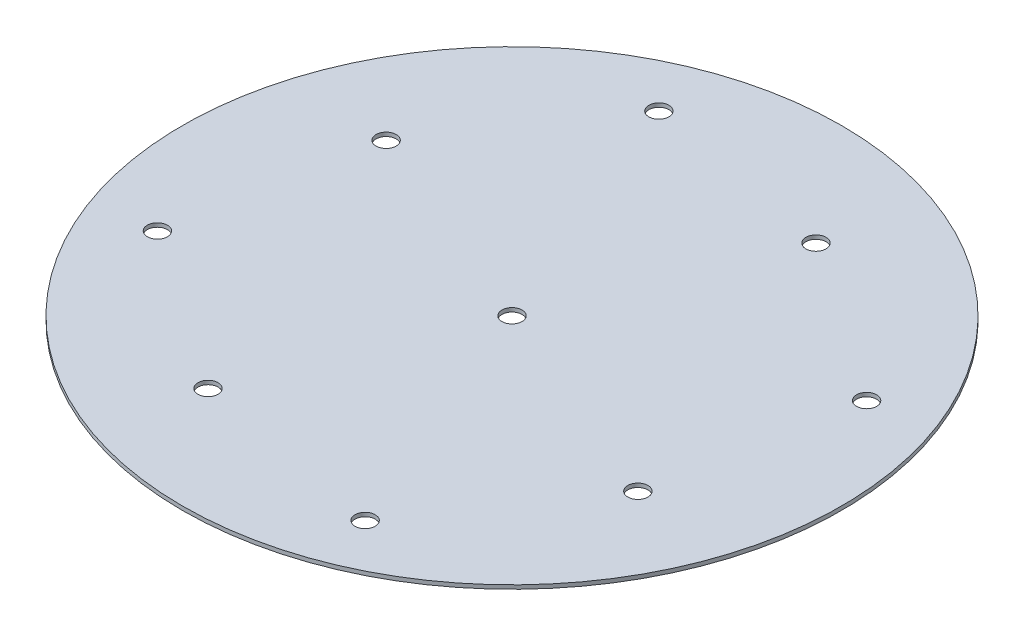
SolidWorks part; units mm, degrees
ref_plane "Front Plane" through (0, 0, 0) normal (0, 0, 1) x (1, 0, 0)
ref_plane "Top Plane" through (0, 0, 0) normal (0, 1, 0) x (1, 0, 0)
ref_plane "Right Plane" through (0, 0, 0) normal (1, 0, 0) x (0, 0, -1)
sketch "Sketch2" plane through (0, 0, 0) normal (1, 0, 0) x (0, 0, -1)
  line L0 (0, 0) -> (-84.9998, 0)
  line L1 (-84.9998, 0) -> (-84.9998, 1)
  line L2 (-84.9998, 1) -> (0, 1)
  line L5 (0, 1) -> (0, 0)
  dimension "D1" = 84.9998
  dimension "D2" = 1
ref_axis "Axis1" through (0, -0.05, 0) along (0, 1, 0)
revolve "Revolve1" add sketch "Sketch2" angle 360 about axis through (0, -0.05, 0) along (0, 1, 0)
hole_wizard "#6 (0.204) Diameter Hole1" positions "Sketch6" profile "Sketch7" hole size "#6" standard "ANSI Inch" end condition through all
sketch "Sketch6" plane through (0, 1, 0) normal (0, 1, 0) x (1, 0, 0)
  line L0 (0, 0) -> (-53.438, 129.0108) construction
  line L2 (0, 0) -> (0, 109.0908) construction
  line L3 (0, 0) -> (-78.5296, 32.528) construction
  circle A0 centre (0, 0) radius 84.9998 construction
  point P0 (-26.7878, 64.6716)
  point P11 (264.7437, 73.7878)
  point P20 (-55.4328, 22.961)
  dimension "D1" = 22.5
  dimension "D2" = 70
  dimension "D3" = 60
  dimension "D4" = 45
sketch "Sketch7" plane through (-26.7878, 1, -64.6716) normal (1, 0, 0) x (0, 0, 1)
  line L0 (0, 0) -> (0, 1)
  line L1 (0, 1) -> (2.5908, 1)
  line L2 (2.5908, 1) -> (2.5908, 0)
  line L5 (2.5908, 0) -> (0, 0)
  line L11 (0, -6.35) -> (0, 107.95) construction
  dimension "Thru Hole Dia." = 5.1816
  dimension "Thru Hole Depth" = 1
pattern_circular "CirPattern3" count 4 over 360 about axis through (0, -0.05, 0) along (0, 1, 0) of "#6 (0.204) Diameter Hole1"
hole_wizard "#6 (0.204) Diameter Hole2" positions "Sketch8" profile "Sketch9" hole size "#6" standard "ANSI Inch" end condition through all
sketch "Sketch8" plane through (0, 1, 0) normal (0, 1, 0) x (1, 0, 0)
  line L0 (0, 0) -> (106.3094, -1.7118) construction
  point P7 (0, 0)
sketch "Sketch9" plane through (0, 1, 0) normal (1, 0, 0) x (0, 0, 1)
  line L0 (0, 0) -> (0, 1)
  line L1 (0, 1) -> (2.5908, 1)
  line L2 (2.5908, 1) -> (2.5908, 0)
  line L5 (2.5908, 0) -> (0, 0)
  line L11 (0, -6.35) -> (0, 107.95) construction
  dimension "Thru Hole Dia." = 5.1816
  dimension "Thru Hole Depth" = 1
equation "\"TubeDiameter\" = 6.6929in"
equation "\"D1@Sketch2\"=\"TubeDiameter\"/2"
